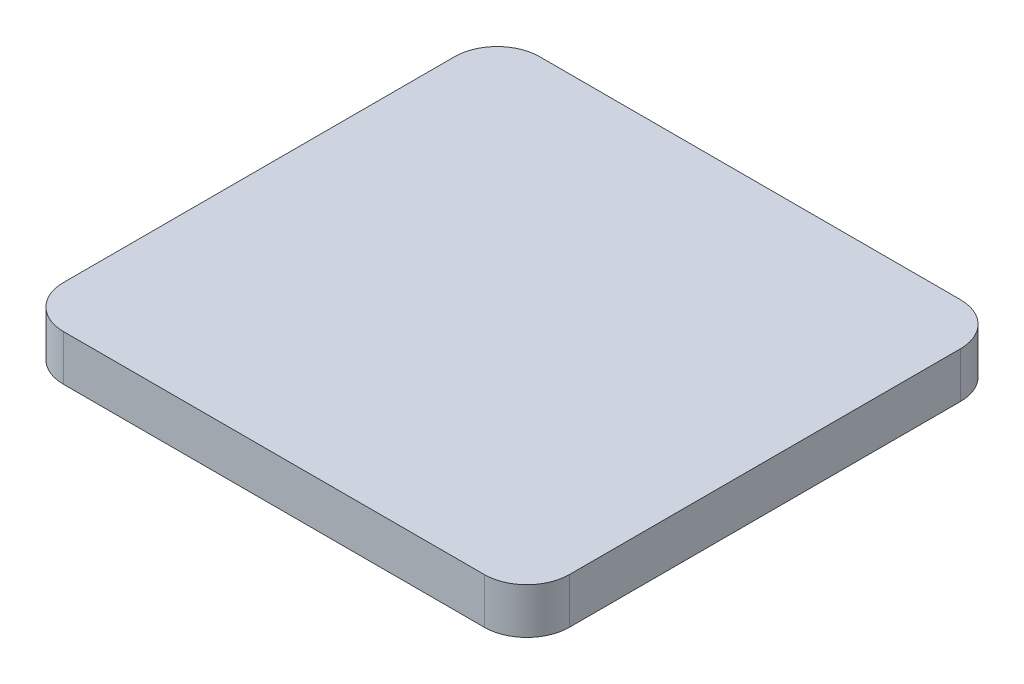
SolidWorks part; units mm, degrees
ref_plane "Front Plane" through (0, 0, 0) normal (0, 0, 1) x (1, 0, 0)
ref_plane "Top Plane" through (0, 0, 0) normal (0, 1, 0) x (1, 0, 0)
ref_plane "Right Plane" through (0, 0, 0) normal (1, 0, 0) x (0, 0, -1)
sketch "Sketch1" plane through (0, 0, 0) normal (0, 1, 0) x (1, 0, 0)
  line L0 (-21.8, 20.4) -> (-21.8, 22.4) construction
  line L1 (19.8, 20.4) -> (-19.8, 20.4)
  line L2 (21.8, 18.4) -> (21.8, -18.4)
  line L3 (19.8, -20.4) -> (-19.8, -20.4)
  line L4 (-21.8, 18.4) -> (-21.8, -18.4)
  line L5 (21.8, 20.4) -> (-21.8, -20.4) construction
  line L6 (21.8, -20.4) -> (-21.8, 20.4) construction
  line L7 (23.8, -22.4) -> (-23.8, -22.4)
  line L8 (23.8, -22.4) -> (23.8, 22.4)
  line L9 (23.8, 22.4) -> (-23.8, 22.4)
  line L10 (-23.8, -22.4) -> (-23.8, 22.4)
  line L11 (23.8, -22.4) -> (-23.8, 22.4) construction
  line L12 (23.8, 22.4) -> (-23.8, -22.4) construction
  line L13 (-21.8, 20.4) -> (-23.8, 20.4) construction
  arc A0 (-19.8, -20.4) -> (-21.8, -18.4) centre (-19.8, -18.4) cw
  arc A1 (21.8, -18.4) -> (19.8, -20.4) centre (19.8, -18.4) cw
  arc A2 (19.8, 20.4) -> (21.8, 18.4) centre (19.8, 18.4) cw
  arc A3 (-19.8, 20.4) -> (-21.8, 18.4) centre (-19.8, 18.4) ccw
  circle A4 centre (-19.8, 18.4) radius 4
  circle A5 centre (19.8, 18.4) radius 4
  circle A6 centre (19.8, -18.4) radius 4
  circle A7 centre (-19.8, -18.4) radius 4
  point P0 (0, 0)
  point P6 (0, 0)
  dimension "D4" = 2
  dimension "D1" = 43.6
  dimension "D2" = 40.8
  dimension "D3" = 2
extrude "Boss-Extrude1" add sketch "Sketch1" along normal blind 1.3 contours L1 A4 L4 A3 | A7 L4 A4 L10 | A7 L3 A0 L4 | A7 L7 A6 L3 | A6 L2 A1 L3 | A6 L8 A5 L2 | L2 A5 L1 A2 | A5 L9 A4 L1 region at (18.0679, 0, -20.5056) region at (0, 0, -21.4255) region at (-18.0679, 0, -20.5056) region at (22.8277, 0, 0) region at (23.1727, 0, 16.4528) region at (-22.8277, 0, 0) region at (0, 0, 21.4255) region at (-21.9056, 0, 16.6679)
sketch "Sketch2" plane through (0, 1.3, 0) normal (0, 1, 0) x (1, 0, 0)
  line L4 (-19.8, -22.4) -> (19.8, -22.4)
  line L5 (23.8, -18.4) -> (23.8, 18.4)
  line L6 (19.8, 22.4) -> (-19.8, 22.4)
  line L7 (-23.8, 18.4) -> (-23.8, -18.4)
  line L8 (-19.8, -22.4) -> (19.8, -22.4)
  line L9 (23.8, -18.4) -> (23.8, 18.4)
  line L10 (19.8, 22.4) -> (-19.8, 22.4)
  line L11 (-23.8, 18.4) -> (-23.8, -18.4)
  arc A4 (19.8, -22.4) -> (23.8, -18.4) centre (19.8, -18.4) ccw
  arc A5 (23.8, 18.4) -> (19.8, 22.4) centre (19.8, 18.4) ccw
  arc A6 (-19.8, 22.4) -> (-23.8, 18.4) centre (-19.8, 18.4) ccw
  arc A7 (-23.8, -18.4) -> (-19.8, -22.4) centre (-19.8, -18.4) ccw
  arc A8 (19.8, -22.4) -> (23.8, -18.4) centre (19.8, -18.4) ccw
  arc A9 (23.8, 18.4) -> (19.8, 22.4) centre (19.8, 18.4) ccw
  arc A10 (-19.8, 22.4) -> (-23.8, 18.4) centre (-19.8, 18.4) ccw
  arc A11 (-23.8, -18.4) -> (-19.8, -22.4) centre (-19.8, -18.4) ccw
  dimension "D1" = 0
extrude "Boss-Extrude2" add sketch "Sketch2" along normal blind 1
sketch "Sketch3" plane through (0, 1.3, 0) normal (0, -1, 0) x (1, 0, 0)
  line L0 (-23.8, 0) -> (23.8, 0) construction
  line L1 (-23.8, 18.4) -> (-23.8, -18.4) construction
  line L2 (23.8, 18.4) -> (23.8, -18.4) construction
  line L3 (-23.8, 11.2) -> (23.8, 11.2) construction
  line L4 (0, 11.2) -> (0, 22.4) construction
  line L5 (19.8, 22.4) -> (-19.8, 22.4) construction
  line L6 (0, 11.2) -> (0, 0) construction
  line L7 (-23.8, -11.2) -> (23.8, -11.2) construction
  line L8 (0, 0) -> (4.1348, 4.1348) construction
  line L9 (11.2, -23.8) -> (11.2, 23.8) construction
  line L10 (-11.2, -23.8) -> (-11.2, 23.8) construction
  line L11 (-21.8, -18.4) -> (-21.8, 18.4) construction
  line L12 (-21.8, -18.4) -> (-21.8, 18.4) construction
  line L13 (19.8, -20.4) -> (-19.8, -20.4) construction
  line L14 (21.8, -18.4) -> (21.8, 18.4) construction
  line L15 (19.8, 20.4) -> (-19.8, 20.4) construction
  line L16 (19.8, 20.4) -> (-19.8, 20.4) construction
  circle A0 centre (-21.8, 11.2) radius 0.4
  circle A1 centre (-21.8, 0) radius 0.4
  circle A2 centre (-21.8, -11.2) radius 0.4
  circle A3 centre (-11.2, -20.4) radius 0.4
  circle A4 centre (11.2, -20.4) radius 0.4
  circle A5 centre (21.8, -11.2) radius 0.4
  circle A6 centre (21.8, 0) radius 0.4
  circle A7 centre (21.8, 11.2) radius 0.4
  circle A8 centre (11.2, 20.4) radius 0.4
  circle A9 centre (0, 20.4) radius 0.4
  circle A10 centre (-11.2, 20.4) radius 0.4
  point P56 (-21.6, 0)
  point P57 (21.6, -10.85)
  dimension "D2" = 0.8
  dimension "D1" = 45
extrude "Boss-Extrude3" add sketch "Sketch3" along normal up to surface (1.3 mm away) up to face at (0, 0, 0)
sketch "Sketch4" plane through (0, 0, 0) normal (0, -1, 0) x (1, 0, 0)
  line L0 (-22.8, 18.4) -> (-22.8, -18.4)
  line L1 (-19.8, -21.4) -> (19.8, -21.4)
  line L2 (22.8, -18.4) -> (22.8, 18.4)
  line L3 (19.8, 21.4) -> (-19.8, 21.4)
  line L4 (19.8, 22.4) -> (-19.8, 22.4)
  line L5 (-23.8, 18.4) -> (-23.8, -18.4)
  line L6 (-19.8, -22.4) -> (19.8, -22.4)
  line L7 (23.8, -18.4) -> (23.8, 18.4)
  line L8 (19.8, 22.4) -> (-19.8, 22.4)
  line L9 (-23.8, 18.4) -> (-23.8, -18.4)
  line L10 (-19.8, -22.4) -> (19.8, -22.4)
  line L11 (23.8, -18.4) -> (23.8, 18.4)
  arc A0 (-19.8, 21.4) -> (-22.8, 18.4) centre (-19.8, 18.4) ccw
  arc A1 (-22.8, -18.4) -> (-19.8, -21.4) centre (-19.8, -18.4) ccw
  arc A2 (19.8, -21.4) -> (22.8, -18.4) centre (19.8, -18.4) ccw
  arc A3 (22.8, 18.4) -> (19.8, 21.4) centre (19.8, 18.4) ccw
  arc A4 (-19.8, 22.4) -> (-23.8, 18.4) centre (-19.8, 18.4) ccw
  arc A5 (-23.8, -18.4) -> (-19.8, -22.4) centre (-19.8, -18.4) ccw
  arc A6 (19.8, -22.4) -> (23.8, -18.4) centre (19.8, -18.4) ccw
  arc A7 (23.8, 18.4) -> (19.8, 22.4) centre (19.8, 18.4) ccw
  arc A8 (-19.8, 22.4) -> (-23.8, 18.4) centre (-19.8, 18.4) ccw
  arc A9 (-23.8, -18.4) -> (-19.8, -22.4) centre (-19.8, -18.4) ccw
  arc A10 (19.8, -22.4) -> (23.8, -18.4) centre (19.8, -18.4) ccw
  arc A11 (23.8, 18.4) -> (19.8, 22.4) centre (19.8, 18.4) ccw
  dimension "D1" = 0
  dimension "D2" = 1
extrude "Boss-Extrude4" add sketch "Sketch4" along normal blind 2
